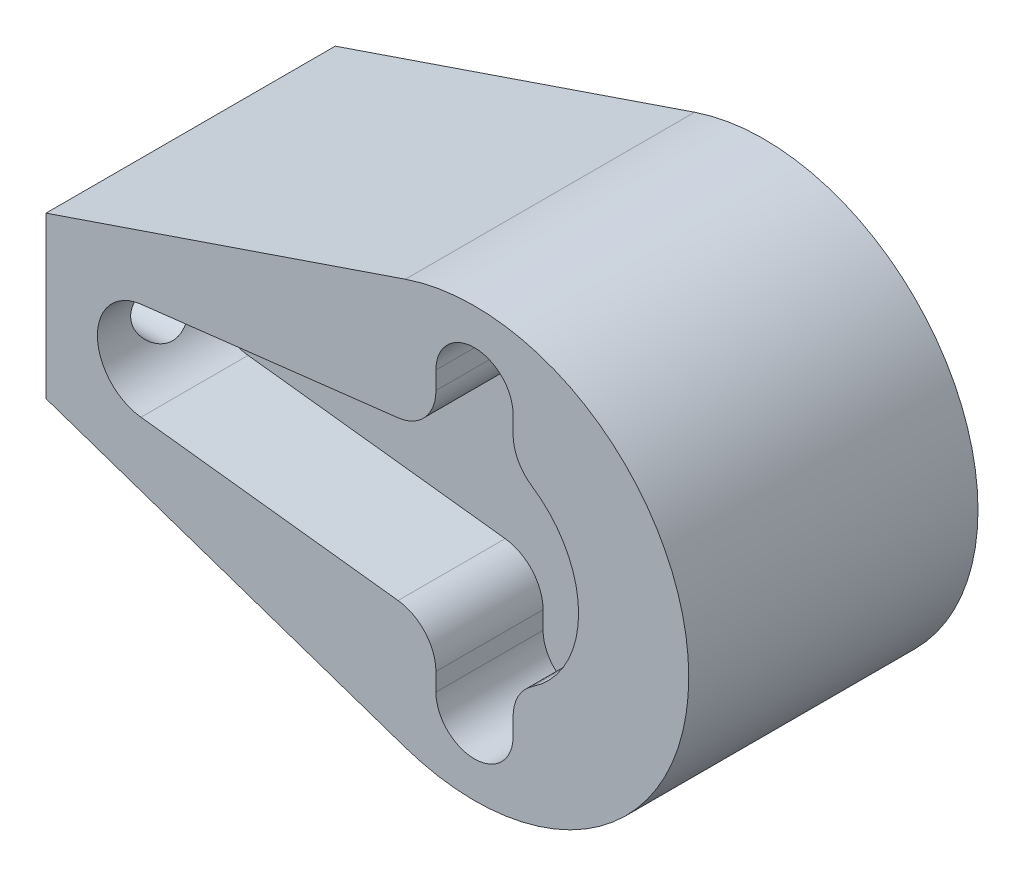
SolidWorks part; units mm, degrees
ref_plane "Спереди" through (0, 0, 0) normal (0, 0, 1) x (1, 0, 0)
ref_plane "Сверху" through (0, 0, 0) normal (0, 1, 0) x (1, 0, 0)
ref_plane "Справа" through (0, 0, 0) normal (1, 0, 0) x (0, 0, -1)
sketch "Эскиз1" plane through (0, 0, 0) normal (0, 0, 1) x (1, 0, 0)
  line L6 (1.8, 5.7088) -> (1.8, 6.512)
  line L7 (-1.8, 6.512) -> (-1.8, 5.679)
  line L8 (-3.5669, 3.6927) -> (-15.5681, 2.2843)
  line L9 (-15.5681, -2.2843) -> (-3.5669, -3.6927)
  line L10 (-1.8, -5.679) -> (-1.8, -6.512)
  line L11 (1.8, -6.512) -> (1.8, -5.7088)
  line L12 (-20, 3.75) -> (-20, -3.75)
  line L13 (-20, 3.75) -> (-3.2252, 9.4656)
  line L15 (-3.2252, -9.4656) -> (-20, -3.75)
  arc A5 (1.8, 6.512) -> (-1.8, 6.512) centre (0, 6.512) ccw
  arc A6 (-15.5681, 2.2843) -> (-15.5681, -2.2843) centre (-15.3, 0) ccw
  arc A7 (-1.8, -6.512) -> (1.8, -6.512) centre (0, -6.512) ccw
  arc A8 (-3.2252, -9.4656) -> (-3.2252, 9.4656) centre (0, 0) ccw
  arc A9 (2.6918, 4.0439) -> (2.6918, -4.0439) centre (0, 0) cw
  arc A10 (-1.8, -5.679) -> (-3.5669, -3.6927) centre (-3.8, -5.679) ccw
  arc A11 (-1.8, 5.679) -> (-3.5669, 3.6927) centre (-3.8, 5.679) cw
  arc A12 (2.6918, -4.0439) -> (1.8, -5.7088) centre (3.8, -5.7088) ccw
  arc A13 (2.6918, 4.0439) -> (1.8, 5.7088) centre (3.8, 5.7088) cw
  point P44 (-1.8, -3.9)
  point P47 (-1.8, 3.9)
  point P52 (1.8, 4.512)
  dimension "D3" = 2.3
  dimension "D4" = 1.8
  dimension "D5" = 7.8
  dimension "D9" = 20
  dimension "D12" = 2
  dimension "D13" = 2
  dimension "D1" = 3.6
  dimension "D2" = 15.3
  dimension "D6" = 2
  dimension "D7" = 1.8
  dimension "D8" = 2.612
  dimension "D10" = 7.5
  dimension "D11" = 20
extrude "Бобышка-Вытянуть1" add sketch "Эскиз1" along normal blind 5
sketch "Эскиз2" plane through (0, 0, 5) normal (0, 0, 1) x (1, 0, 0)
  line L3 (-3.2252, 9.4656) -> (-20, 3.75)
  line L4 (-20, 3.75) -> (-20, -3.75)
  line L5 (-20, -3.75) -> (-3.2252, -9.4656)
  line L6 (-3.2252, 9.4656) -> (-20, 3.75)
  line L7 (-20, 3.75) -> (-20, -3.75)
  line L8 (-20, -3.75) -> (-3.2252, -9.4656)
  arc A1 (-3.2252, -9.4656) -> (-3.2252, 9.4656) centre (0, 0) ccw
  arc A2 (-3.2252, -9.4656) -> (-3.2252, 9.4656) centre (0, 0) ccw
  dimension "D1" = 0
extrude "Бобышка-Вытянуть2" add sketch "Эскиз2" against normal blind 8.5 from surface starting at face at (-8.3063, 0, 0)
sketch "Эскиз3" plane through (0, 0, -8.5) normal (0, 0, -1) x (-1, 0, 0)
  circle A0 centre (0, 0) radius 2.75
  dimension "D1" = 5.5
extrude "Бобышка-Вытянуть3" add sketch "Эскиз3" along normal blind 3
sketch "Эскиз4" plane through (-20, 0, 0) normal (-1, 0, 0) x (0, 0, 1)
  line L0 (-1000, 0) -> (49000, 0) construction
  line L2 (-8.5, 2.75) -> (-8.5, -2.75) construction
  line L3 (5, 3.75) -> (5, -3.75) construction
  circle A0 centre (-5.5, 0) radius 1.45
  circle A1 centre (2, 0) radius 1.45
  dimension "D1" = 2.9
  dimension "D2" = 3
  dimension "D3" = 3
extrude "Вырез-Вытянуть1" cut sketch "Эскиз4" against normal blind 7
